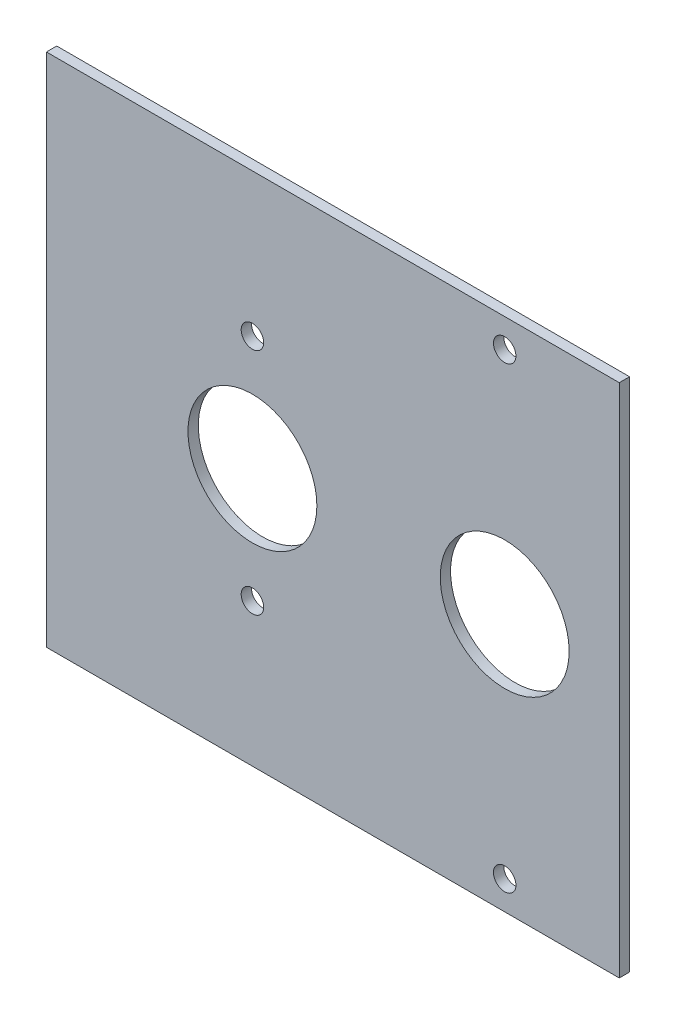
SolidWorks part; units mm, degrees
ref_plane "Front Plane" through (0, 0, 0) normal (0, 0, 1) x (1, 0, 0)
ref_plane "Top Plane" through (0, 0, 0) normal (0, 1, 0) x (1, 0, 0)
ref_plane "Right Plane" through (0, 0, 0) normal (1, 0, 0) x (0, 0, -1)
sketch "Sketch1" plane through (0, 0, 0) normal (0, 0, 1) x (1, 0, 0)
  line L1 (0, 0) -> (127, 0)
  line L2 (0, 0) -> (0, 114.3)
  line L3 (0, 114.3) -> (127, 114.3)
  line L4 (127, 0) -> (127, 114.3)
  circle A0 centre (45.6692, 82.55) radius 2.4892
  circle A1 centre (45.6692, 57.15) radius 14.2875
  circle A2 centre (45.6692, 31.75) radius 2.4892
  circle A3 centre (101.6, 107.95) radius 2.4892
  circle A4 centre (101.6, 57.15) radius 14.2875
  circle A5 centre (101.6, 6.35) radius 2.4892
  dimension "D3" = 25.4
  dimension "D10" = 25.4
  dimension "D12" = 4.9784
  dimension "D13" = 4.9784
  dimension "D14" = 28.575
  dimension "D15" = 28.575
  dimension "D16" = 4.9784
  dimension "D17" = 4.9784
  dimension "D2" = 127
  dimension "D4" = 57.15
  dimension "D5" = 50.8
  dimension "D6" = 50.8
  dimension "D7" = 6.35
  dimension "D8" = 25.4
  dimension "D9" = 25.4
  dimension "D11" = 114.3
  dimension "D18" = 55.9308
extrude "Boss-Extrude1" add sketch "Sketch1" along normal mid plane 2.286
